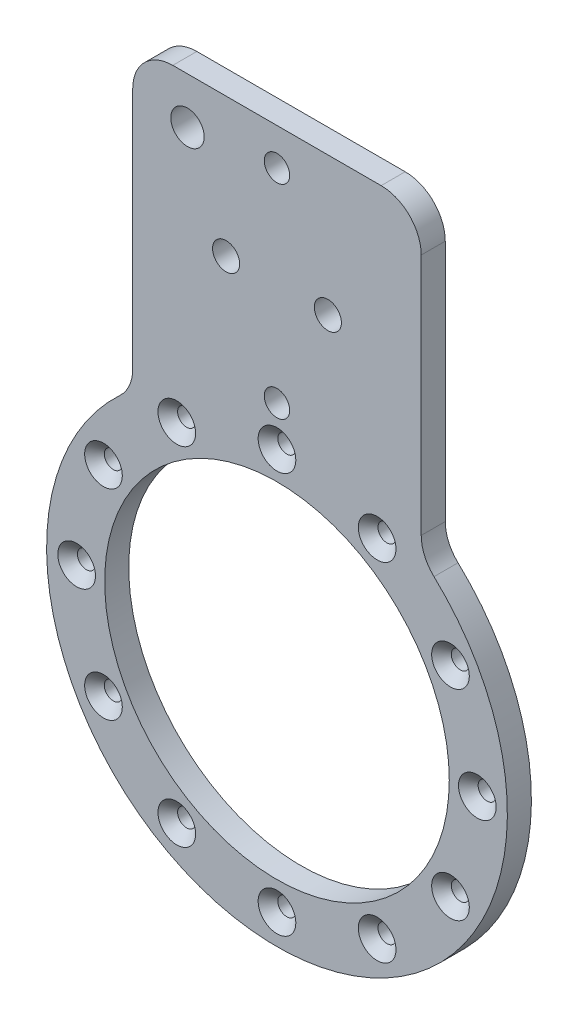
SolidWorks part; units mm, degrees
material "6061-T6 (SS)"
ref_plane "Front Plane" through (0, 0, 0) normal (0, 0, 1) x (1, 0, 0)
ref_plane "Top Plane" through (0, 0, 0) normal (0, 1, 0) x (1, 0, 0)
ref_plane "Right Plane" through (0, 0, 0) normal (1, 0, 0) x (0, 0, -1)
sketch "Sketch1" plane through (0, 0, 0) normal (0, 0, 1) x (1, 0, 0)
  line L0 (-36, 44.8358) -> (-36, 120)
  line L1 (-36, 120) -> (36, 120)
  line L2 (36, 120) -> (36, 44.8358)
  circle A0 centre (0, 0) radius 43
  circle A1 centre (0, 0) radius 50 construction
  arc A2 (-36, 44.8358) -> (36, 44.8358) centre (0, 0) ccw
  point P7 (0, 120)
  dimension "D2" = 115
  dimension "D3" = 100
  dimension "D4" = 86
  dimension "D1" = 120
  dimension "D5" = 72
extrude "base" add sketch "Sketch1" along normal mid plane 6
hole_wizard "M4 Clearance Hole1" positions "Sketch3" profile "Sketch4" hole size "M4" standard "ISO" end condition through all
sketch "Sketch3" plane through (0, 0, 3) normal (0, 0, 1) x (1, 0, 0)
  point P0 (0, 50)
  point P16 (25, 43.3013)
  point P17 (43.3013, 25)
  point P18 (50, 0)
  point P19 (43.3013, -25)
  point P20 (25, -43.3013)
  point P21 (0, -50)
  point P22 (-25, -43.3013)
  point P23 (-43.3013, -25)
  point P24 (-50, 0)
  point P25 (-43.3013, 25)
  point P26 (-25, 43.3013)
  dimension "D1" = 50
  dimension "D3" = 50
  dimension "D2" = 12
sketch "Sketch4" plane through (0, 50, 3) normal (1, 0, 0) x (0, -1, 0)
  line L0 (0, 0) -> (0, 6)
  line L1 (0, 6) -> (2.25, 6)
  line L2 (2.25, 6) -> (2.25, 0)
  line L5 (2.25, 0) -> (0, 0)
  line L11 (0, -6.35) -> (0, 107.95) construction
  dimension "Thru Hole Dia." = 4.5
  dimension "Thru Hole Depth" = 6
hole_wizard "M4 Clearance Hole2" positions "Sketch5" profile "Sketch6" hole size "M4" standard "ISO" end condition through all
sketch "Sketch5" plane through (0, 0, 3) normal (0, 0, 1) x (1, 0, 0)
  point P0 (0, 60)
  point P2 (0, 110.8)
  dimension "D1" = 60
  dimension "D2" = 50.8
sketch "Sketch6" plane through (0, 60, 3) normal (1, 0, 0) x (0, -1, 0)
  line L0 (0, 0) -> (0, 6)
  line L1 (0, 6) -> (3.175, 6)
  line L2 (3.175, 6) -> (3.175, 0)
  line L5 (3.175, 0) -> (0, 0)
  line L11 (0, -6.35) -> (0, 107.95) construction
  dimension "Thru Hole Dia." = 6.35
  dimension "Thru Hole Depth" = 6
hole_wizard "1/4 Clearance Hole1" positions "Sketch7" profile "Sketch8" hole size "1/4" standard "ANSI Inch" end condition through all
sketch "Sketch7" plane through (0, 0, 3) normal (0, 0, 1) x (1, 0, 0)
  circle A0 centre (0, 110.8) radius 3.175 construction
  point P0 (-12.7, 85.4)
  point P2 (12.7, 85.4)
  dimension "D3" = 25.4
  dimension "D1" = 25.4
  dimension "D2" = 12.7
sketch "Sketch8" plane through (-12.7, 85.4, 3) normal (1, 0, 0) x (0, -1, 0)
  line L0 (0, 0) -> (0, 6)
  line L1 (0, 6) -> (3.3782, 6)
  line L2 (3.3782, 6) -> (3.3782, 0)
  line L5 (3.3782, 0) -> (0, 0)
  line L11 (0, -6.35) -> (0, 107.95) construction
  dimension "Thru Hole Dia." = 6.7564
  dimension "Thru Hole Depth" = 6
fillet "Fillet1" radius 10 4 edges at (36, 120, 0) (-36, 120, 0) (-36, 44.8358, 0) (36, 44.8358, 0)
sketch "Sketch9" plane through (0, 0, 3) normal (0, 0, 1) x (1, 0, 0)
  line L0 (57.5, 0) -> (63.85, 0)
  line L1 (49, -30.0874) -> (51.6912, -37.4813)
  arc A0 (49, -30.0874) -> (57.5, 0) centre (0, 0) ccw
  arc A1 (-39.1852, 42.0805) -> (39.1852, 42.0805) centre (0, 0) ccw construction
  arc A2 (63.85, 0) -> (51.6912, -37.4813) centre (0, 0) cw
  dimension "D1" = 20
  dimension "D2" = 6.35
  dimension "D3" = 8.5
extrude "stoper" [suppressed] add sketch "Sketch9" along normal blind 20 and the other way up to surface
ref_axis "Axis1" through (0, 0, 3) along (0, 0, -1)
sketch "Sketch10" plane through (0, 0, 3) normal (0, 0, 1) x (1, 0, 0)
  line L0 (0, 0) -> (0, 43) construction
  circle A0 centre (0, 0) radius 43 construction
hole_wizard "CSK for M4 Flat Head Machine Screw1" positions "Sketch11" profile "Sketch12" countersink size "M4" standard "ANSI Metric" end condition through all
sketch "Sketch11" plane through (0, 0, 3) normal (0, 0, 1) x (1, 0, 0)
  point P0 (0, 50)
  point P4 (25, 43.3013)
  point P7 (43.3013, 25)
  point P10 (50, 0)
  point P13 (43.3013, -25)
  point P16 (25, -43.3013)
  point P19 (0, -50)
  point P22 (-25, -43.3013)
  point P25 (-43.3013, -25)
  point P28 (-50, 0)
  point P31 (-43.3013, 25)
  point P34 (-25, 43.3013)
sketch "Sketch12" plane through (0, 50, 3) normal (1, 0, 0) x (0, -1, 0)
  line L0 (0, 0) -> (0, 6)
  line L1 (0, 6) -> (2.25, 6)
  line L2 (2.25, 6) -> (2.25, 2.45)
  line L3 (2.25, 2.45) -> (4.7, 0)
  line L5 (4.7, 0) -> (0, 0)
  line L6 (-2.25, 2.45) -> (-4.7, 0) construction
  line L11 (0, -6.35) -> (0, 107.95) construction
  dimension "Thru Hole Dia." = 4.5
  dimension "Thru Hole Depth" = 6
  dimension "Near C'Sink Dia." = 9.4
  dimension "Near C'Sink Angle" = 90
sketch "Sketch15" plane through (0, 0, -3) normal (0, 0, -1) x (-1, 0, 0)
  line L2 (36, 110) -> (36, 49.3989) construction
  line L3 (-26, 120) -> (26, 120) construction
  circle A1 centre (22.335, 108.435) radius 4.165
  dimension "D1" = 8.33
  dimension "D2" = 13.665
  dimension "D3" = 11.565
extrude "Cut-Extrude1" cut sketch "Sketch15" against normal through all contours A1
